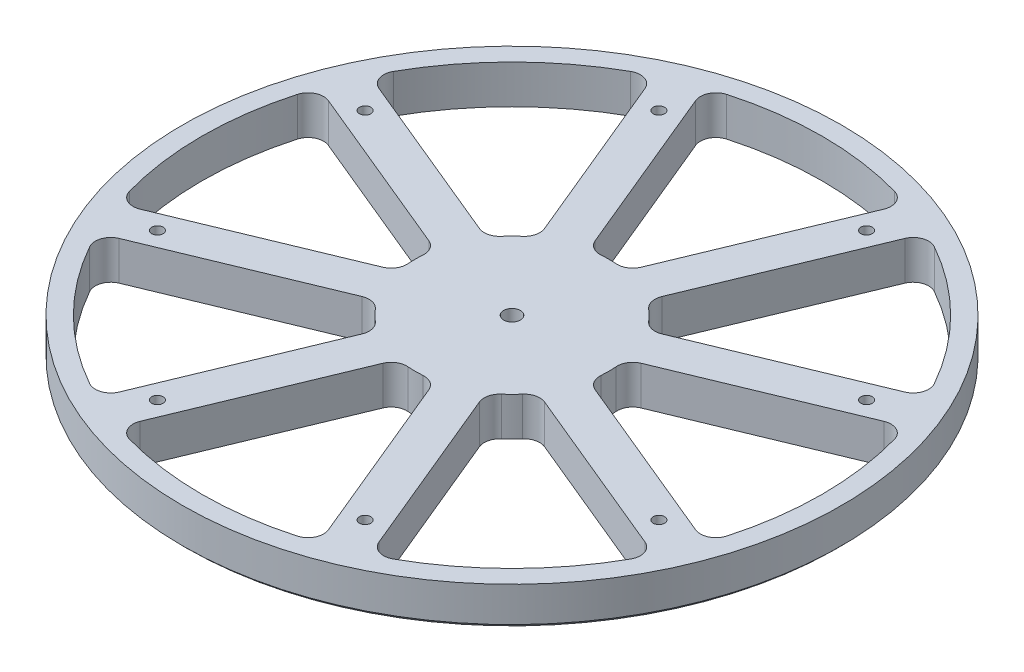
SolidWorks part; units mm, degrees
ref_plane "Front Plane" through (0, 0, 0) normal (0, 0, 1) x (1, 0, 0)
ref_plane "Top Plane" through (0, 0, 0) normal (0, 1, 0) x (1, 0, 0)
ref_plane "Right Plane" through (0, 0, 0) normal (1, 0, 0) x (0, 0, -1)
sketch "Sketch2" plane through (0, 0, 0) normal (1, 0, 0) x (0, 0, -1)
  line L0 (0, 0) -> (-84.9998, 0)
  line L1 (-84.9998, 0) -> (-84.9998, 10)
  line L2 (-84.9998, 10) -> (0, 10)
  line L5 (0, 10) -> (0, 0)
  dimension "D1" = 84.9998
  dimension "D2" = 10
ref_axis "Axis1" through (0, -0.75, 0) along (0, 1, 0)
revolve "Revolve1" add sketch "Sketch2" angle 360 about axis through (0, -0.75, 0) along (0, 1, 0)
hole_wizard "#32 (0.116) Diameter Hole1" positions "Sketch6" profile "Sketch7" hole size "#32" standard "ANSI Inch" end condition through all
sketch "Sketch6" plane through (0, 10, 0) normal (0, 1, 0) x (1, 0, 0)
  line L0 (0, 0) -> (-53.438, 129.0108) construction
  line L2 (0, 0) -> (0, 109.0908) construction
  point P0 (-26.7878, 64.6716)
  dimension "D1" = 22.5
  dimension "D2" = 70
sketch "Sketch7" plane through (-26.7878, 10, -64.6716) normal (1, 0, 0) x (0, 0, 1)
  line L0 (0, 0) -> (0, 10)
  line L1 (0, 10) -> (1.4732, 10)
  line L2 (1.4732, 10) -> (1.4732, 0)
  line L5 (1.4732, 0) -> (0, 0)
  line L11 (0, -6.35) -> (0, 107.95) construction
  dimension "Thru Hole Dia." = 2.9464
  dimension "Thru Hole Depth" = 10
pattern_circular "CirPattern3" count 8 over 360 about axis through (0, -0.75, 0) along (0, 1, 0) of "#32 (0.116) Diameter Hole1"
sketch "Sketch8" plane through (0, 10, 0) normal (0, 1, 0) x (1, 0, 0)
  line L4 (0, 0) -> (0, 93.9995) construction
  line L5 (0, 0) -> (113.8372, 0) construction
  line L6 (-4.7544, 24.5438) -> (-25.9354, 75.6791)
  line L7 (4.7544, 24.5438) -> (25.9354, 75.6791)
  line L8 (0, 0) -> (-26.7878, 64.6716) construction
  arc A0 (-4.7544, 24.5438) -> (4.7544, 24.5438) centre (0, 0) cw
  arc A1 (-25.9354, 75.6791) -> (25.9354, 75.6791) centre (0, 0) cw
  circle A2 centre (0, 0) radius 84.9998 construction
  dimension "D1" = 25
  dimension "D2" = 5
  dimension "D3" = 5
extrude "Cut-Extrude1" cut sketch "Sketch8" against normal through all
fillet "Fillet1" radius 4 4 edges at (4.7544, 5, -24.5438) (25.9354, 5, -75.6791) (-4.7544, 5, -24.5438) (-25.9354, 5, -75.6791)
pattern_circular "CirPattern4" count 8 over 360 about axis through (0, -0.75, 0) along (0, 1, 0) of "Cut-Extrude1", "Fillet1"
chamfer "Chamfer2" distance 1 angle 45 1 edges at (0, 0, -84.9998)
hole_wizard "#18 (0.1695) Diameter Hole1" positions "Sketch9" profile "Sketch11" hole size "#18" standard "ANSI Inch" end condition through all
sketch "Sketch9" plane through (0, 0, 0) normal (0, -1, 0) x (-1, 0, 0)
  point P0 (0, 0)
sketch "Sketch11" plane through (0, 0, 0) normal (1, 0, 0) x (0, 0, -1)
  line L0 (0, 0) -> (0, 10)
  line L1 (0, 10) -> (2.1526, 10)
  line L2 (2.1526, 10) -> (2.1526, 0)
  line L5 (2.1526, 0) -> (0, 0)
  line L11 (0, -6.35) -> (0, 107.95) construction
  dimension "Thru Hole Dia." = 4.3053
  dimension "Thru Hole Depth" = 10
